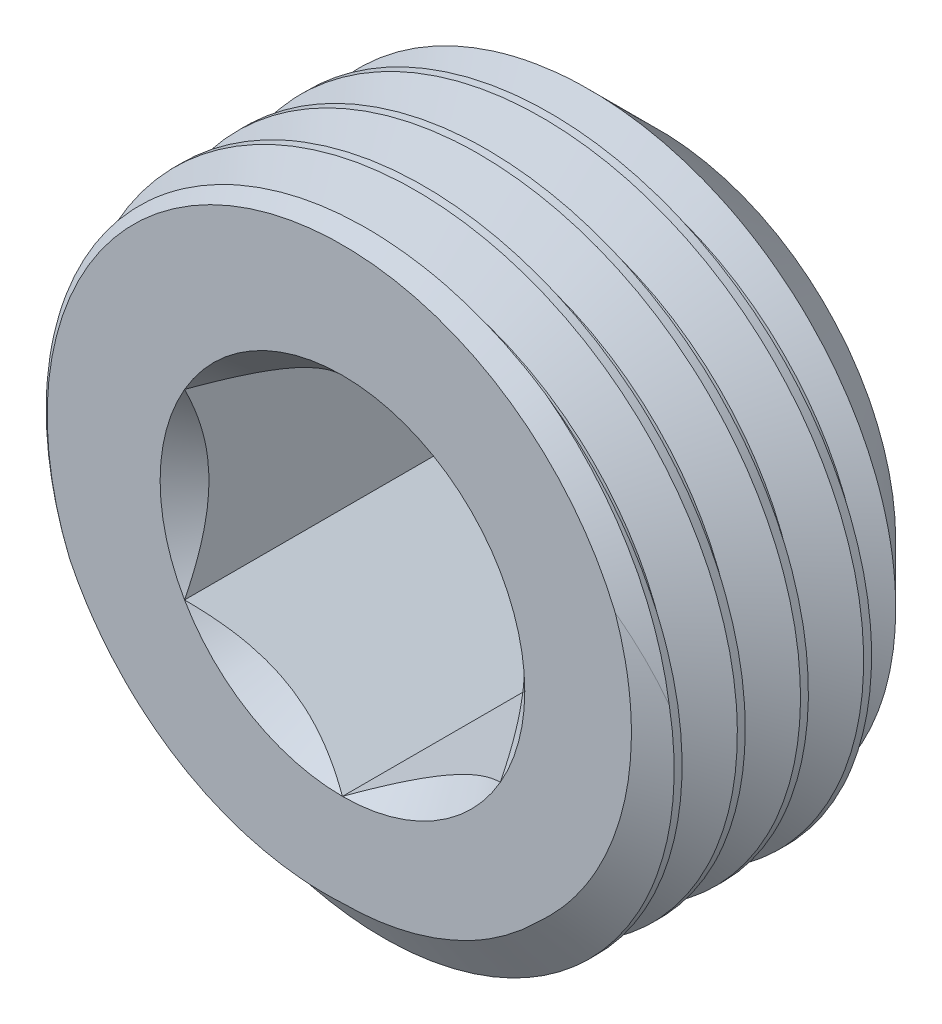
SolidWorks part; units mm, degrees
material "Alloy Steel"
ref_plane "Front Plane" through (0, 0, 0) normal (0, 0, 1) x (1, 0, 0)
ref_plane "Top Plane" through (0, 0, 0) normal (0, 1, 0) x (1, 0, 0)
ref_plane "Right Plane" through (0, 0, 0) normal (1, 0, 0) x (0, 0, -1)
sketch "Sketch1" plane through (0, 0, 0) normal (1, 0, 0) x (0, 0, -1)
  line L0 (3.9751, 0) -> (-3.9751, 0) construction
  line L1 (0, -6.35) -> (0, 6.35) construction
  line L2 (3.9751, 6.35) -> (-3.9751, 6.35) construction
  line L3 (-3.9751, 6.35) -> (-3.9751, 0) construction
  line L4 (3.9751, 0) -> (3.9751, 6.35) construction
  line L5 (-3.9751, -3.175) -> (-3.9751, 3.175) construction
  line L6 (-3.9751, 0) -> (-3.9751, -6.35) construction
  line L7 (0.8001, 6.35) -> (3.9751, 3.175) construction
  line L8 (3.9751, 3.175) -> (0.8001, 0) construction
  line L9 (-5.1657, 6.4875) -> (-3.8957, 6.4875)
  line L10 (-3.8957, 6.4875) -> (-4.5307, 5.3876)
  line L11 (-4.5307, 5.3876) -> (-5.1657, 6.4875)
  line L12 (-4.5307, 6.4875) -> (-4.5307, 6.35)
  line L13 (-5.0863, 6.35) -> (-3.9751, 6.35)
  line L14 (-5.126, 6.4187) -> (-3.9354, 6.4187)
  line L15 (-4.5307, 5.5251) -> (-4.5307, 5.3876)
  line L16 (-4.6101, 5.5251) -> (-4.4513, 5.5251)
  point P3 (-2.0701, -6.35)
  point P4 (0, 0)
  point P8 (0, 0)
  point P11 (0, 6.35)
  point P14 (-3.9751, 0)
  point P25 (0.7874, 0)
  point P27 (-4.5307, 6.35)
  point P30 (-4.5307, 6.4187)
  point P32 (-4.5307, 5.5251)
  dimension "Drive Size" = 6.35
  dimension "Screw Size Decimal Equivalent" = 12.7
  dimension "Length" = 7.9502
  dimension "Pitch" = 1.27
  dimension "D2" = 0.1588
  dimension "Drive Depth" = 4.7625
  dimension "D1" = 1.905
sketch "Sketch2" plane through (0, 0, 0) normal (1, 0, 0) x (0, 0, -1)
  line L0 (-3.9751, 5.9376) -> (-3.6863, 6.35)
  line L1 (-3.9751, 6.35) -> (-3.9751, 0) construction
  line L2 (3.9751, 6.35) -> (-3.9751, 6.35) construction
  line L3 (-3.6863, 6.35) -> (0.8001, 6.35)
  line L4 (0.8001, 6.35) -> (3.9751, 3.175)
  line L5 (3.9751, 0) -> (3.9751, 6.35) construction
  line L6 (3.9751, 3.175) -> (0.8001, 0)
  line L7 (0.8001, 0) -> (-3.9751, 0)
  line L8 (-3.9751, 0) -> (-3.9751, 5.9376)
  line L9 (-4.2132, 5.9376) -> (-3.9751, 5.9376) construction
  line L11 (-3.8957, 6.4875) -> (-4.5307, 5.3876) construction
  dimension "D1" = 35
revolve "Revolve1" add sketch "Sketch2" angle 360 about L7
sketch "Sketch3" plane through (0, 0, 3.9751) normal (0, 0, 1) x (1, 0, 0)
  line L1 (0, 3.6662) -> (-3.175, 1.8331)
  line L2 (-3.175, 1.8331) -> (-3.175, -1.8331)
  line L3 (-3.175, -1.8331) -> (0, -3.6662)
  line L4 (0, -3.6662) -> (3.175, -1.8331)
  line L5 (3.175, -1.8331) -> (3.175, 1.8331)
  line L6 (3.175, 1.8331) -> (0, 3.6662)
  circle A0 centre (0, 0) radius 3.175 construction
extrude "Cut-Extrude1" cut sketch "Sketch3" against normal through all
sketch "Sketch4" plane through (0, 0, 3.9751) normal (0, 0, 1) x (1, 0, 0)
  circle A0 centre (0, 0) radius 3.6662
extrude "Cut-Extrude2" cut sketch "Sketch4" against normal blind 2.54 draft 45
sketch "Sketch6" plane through (0, 0, 3.9751) normal (0, 0, 1) x (1, 0, 0)
  circle A0 centre (0, 0) radius 6.35
curve "Helix/Spiral1" pitch 1.27 height 9.2202 radius 6.35 centre (0, 0, 3.9751) axis (0, 0, -1) start towards (0, 1, 0)
sketch "Sketch7" plane through (0, 0, 0) normal (1, 0, 0) x (0, 0, -1)
  line L0 (-5.126, 6.4187) -> (-3.9354, 6.4187)
  line L1 (-3.9354, 6.4187) -> (-4.4513, 5.5251)
  line L2 (-4.4513, 5.5251) -> (-4.6101, 5.5251)
  line L3 (-4.6101, 5.5251) -> (-5.126, 6.4187)
sweep "Cut-Sweep1" cut profiles "Sketch7" path "Helix/Spiral1"
ref_axis "Axis1" through (0, 0, -5.6844) along (0, 0, 1)
sketch "Sketch8" plane through (0, 0, 0) normal (1, 0, 0) x (0, 0, -1)
  line L0 (2.3749, 0) -> (2.3749, -6.8439)
  line L1 (2.3749, -6.8439) -> (6.8135, -6.8439)
  line L2 (6.8135, -6.8439) -> (6.8135, 0)
  line L3 (6.8135, 0) -> (2.3749, 0)
  line L4 (-3.9751, 2.2722) -> (-3.9751, -3.9068) construction
  line L5 (4.6529, 0) -> (-4.6529, 0) construction
  dimension "D1" = 6.35
revolve "Cut-Revolve1" cut sketch "Sketch8" angle 360 about axis through (0, 0, -5.6844) along (0, 0, 1)
equation "\"D2@Sketch1\" = \"Pitch@Sketch1\" / 8"
equation "\"Drive Depth@Sketch1\"=\"Drive Size@Sketch1\"*.75"
equation "\"D3@Helix/Spiral1\" = \"Length@Sketch1\" + \"Pitch@Sketch1\""
equation "\"D4@Helix/Spiral1\"=\"Pitch@Sketch1\""
equation "\"D1@Sketch1\"=\"Pitch@Sketch1\"*1.5"
